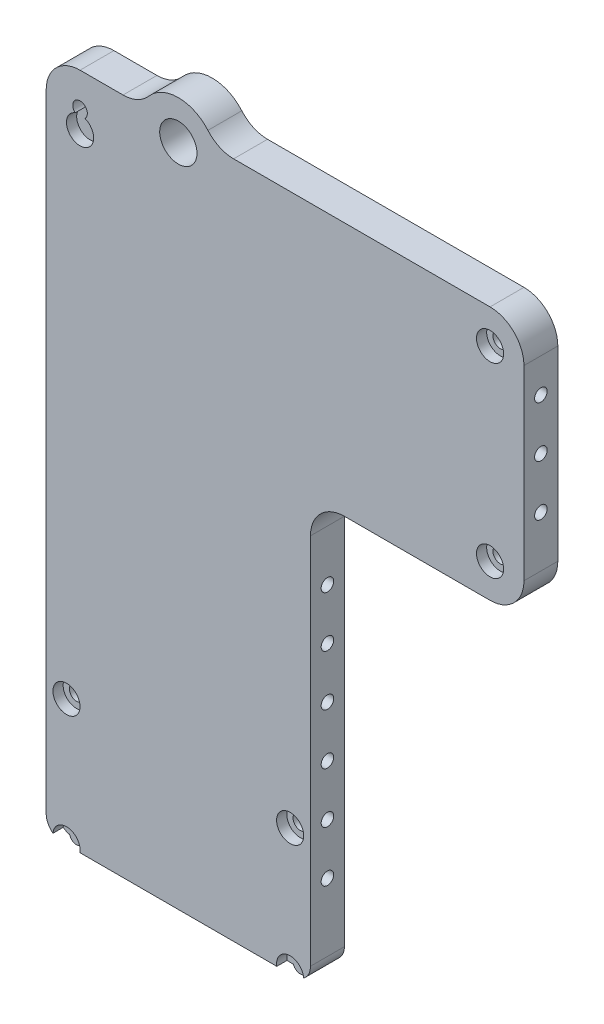
SolidWorks part; units mm, degrees
material "Petg 30% Infill"
ref_plane "Front Plane" through (0, 0, 0) normal (0, 0, 1) x (1, 0, 0)
ref_plane "Top Plane" through (0, 0, 0) normal (0, 1, 0) x (1, 0, 0)
ref_plane "Right Plane" through (0, 0, 0) normal (1, 0, 0) x (0, 0, -1)
sketch "Sketch1" plane through (0, 0, 0) normal (0, 0, 1) x (1, 0, 0)
  line L11 (-3.4368, 18.0423) -> (-3.4368, 128.0423)
  line L12 (6.5632, 138.0423) -> (49.5503, 138.0423)
  line L13 (59.5503, 148.0423) -> (59.5503, 203.0423)
  line L14 (49.5503, 213.0423) -> (-26.1197, 213.0423)
  line L15 (-58.754, 213.0423) -> (-71.4368, 213.0423)
  line L16 (-81.4368, 203.0423) -> (-81.4368, 18.0423)
  line L17 (-76.4368, 13.0423) -> (-8.4368, 13.0423)
  line L18 (-3.4368, 18.0423) -> (-3.4368, 128.0423)
  line L19 (6.5632, 138.0423) -> (49.5503, 138.0423)
  line L20 (59.5503, 148.0423) -> (59.5503, 203.0423)
  line L21 (49.5503, 213.0423) -> (-26.1197, 213.0423)
  line L22 (-58.754, 213.0423) -> (-71.4368, 213.0423)
  line L23 (-81.4368, 203.0423) -> (-81.4368, 18.0423)
  line L24 (-76.4368, 13.0423) -> (-8.4368, 13.0423)
  circle A0 centre (-42.4368, 209.0423) radius 5.5
  arc A1 (-3.4368, 18.0423) -> (-8.4368, 13.0423) centre (-8.4368, 18.0423) cw
  arc A2 (-81.4368, 18.0423) -> (-76.4368, 13.0423) centre (-76.4368, 18.0423) ccw
  circle A3 centre (-42.4368, 209.0423) radius 5.5 construction
  circle A4 centre (-75.4368, 50.376) radius 2.15
  circle A5 centre (-75.4368, 13.7092) radius 2.15
  circle A6 centre (-9.4368, 13.7092) radius 2.15
  arc A7 (6.5632, 138.0423) -> (-3.4368, 128.0423) centre (6.5632, 128.0423) ccw
  arc A8 (49.5503, 138.0423) -> (59.5503, 148.0423) centre (49.5503, 148.0423) ccw
  arc A9 (59.5503, 203.0423) -> (49.5503, 213.0423) centre (49.5503, 203.0423) ccw
  arc A10 (-33.709, 216.5306) -> (-26.1197, 213.0423) centre (-26.1197, 223.0423) ccw
  arc A11 (-33.709, 216.5306) -> (-51.1646, 216.5306) centre (-42.4368, 209.0423) ccw
  arc A12 (-58.754, 213.0423) -> (-51.1646, 216.5306) centre (-58.754, 223.0423) ccw
  arc A13 (-71.4368, 213.0423) -> (-81.4368, 203.0423) centre (-71.4368, 203.0423) ccw
  arc A14 (6.5632, 138.0423) -> (-3.4368, 128.0423) centre (6.5632, 128.0423) ccw
  arc A15 (49.5503, 138.0423) -> (59.5503, 148.0423) centre (49.5503, 148.0423) ccw
  arc A16 (59.5503, 203.0423) -> (49.5503, 213.0423) centre (49.5503, 203.0423) ccw
  arc A17 (-33.709, 216.5306) -> (-26.1197, 213.0423) centre (-26.1197, 223.0423) ccw
  arc A18 (-33.709, 216.5306) -> (-51.1646, 216.5306) centre (-42.4368, 209.0423) ccw
  arc A19 (-58.754, 213.0423) -> (-51.1646, 216.5306) centre (-58.754, 223.0423) ccw
  arc A20 (-71.4368, 213.0423) -> (-81.4368, 203.0423) centre (-71.4368, 203.0423) ccw
  circle A21 centre (-9.4368, 50.376) radius 2.15
  circle A23 centre (-75.4368, 13.7092) radius 2.2 construction
  circle A24 centre (-75.4368, 50.376) radius 2.2 construction
  circle A25 centre (-9.4368, 13.7092) radius 2.2 construction
  circle A26 centre (-9.4368, 50.376) radius 2.2 construction
  arc A35 (-81.4368, 18.0423) -> (-76.4368, 13.0423) centre (-76.4368, 18.0423) ccw
  arc A36 (-81.4368, 18.0423) -> (-76.4368, 13.0423) centre (-76.4368, 18.0423) ccw
  arc A37 (-8.4368, 13.0423) -> (-3.4368, 18.0423) centre (-8.4368, 18.0423) ccw
  arc A38 (-8.4368, 13.0423) -> (-3.4368, 18.0423) centre (-8.4368, 18.0423) ccw
  dimension "D2" = 4.3
  dimension "D3" = 5
  dimension "D1" = 0
extrude "Boss-Extrude1" add sketch "Sketch1" along normal blind 10 contours A1 L18 A14 L19 A15 L20 A16 L21 A17 A18 A19 L22 A20 L23 A2 L24 | A0 | A21 | A6 | A4 | A5
sketch "Sketch2" plane through (0, 0, 10) normal (0, 0, 1) x (1, 0, 0)
  circle A0 centre (-75.4368, 50.376) radius 4
  circle A1 centre (-9.4368, 50.376) radius 4
  circle A2 centre (-9.4368, 13.7092) radius 4
  circle A3 centre (-75.4368, 13.7092) radius 4
  dimension "D1" = 8
extrude "Cut-Extrude1" cut sketch "Sketch2" against normal blind 3
sketch "Sketch3" plane through (0, 0, 0) normal (0, 0, -1) x (-1, 0, 0)
  circle A0 centre (-21.6596, 190.973) radius 1.85
  circle A1 centre (31.0338, 190.3381) radius 1.85
  circle A2 centre (-21.6596, 190.973) radius 4.85
  circle A3 centre (31.0338, 190.3381) radius 4.85
  dimension "D1" = 3.7
  dimension "D2" = 3
extrude "Boss-Extrude2" add sketch "Sketch3" along normal blind 4
sketch "Sketch5" plane through (0, 0, 0) normal (0, 0, -1) x (-1, 0, 0)
  line L0 (47.5919, 184.6852) -> (47.5919, 70.4633) construction
  line L1 (13.3104, 85.2357) -> (47.5919, 85.2357)
  line L2 (13.3104, 85.2357) -> (13.3104, 70.4633)
  line L3 (13.3104, 70.4633) -> (47.5919, 70.4633)
  line L4 (47.5919, 85.2357) -> (47.5919, 70.4633)
  line L5 (47.5919, 70.4633) -> (-38.9159, 70.4633) construction
extrude "Boss-Extrude3" add sketch "Sketch5" along normal blind 4
sketch "Sketch6" plane through (0, 0, 0) normal (0, 0, -1) x (-1, 0, 0)
  line L0 (13.7834, 69.9633) -> (13.7834, 65.6705)
  line L1 (13.7834, 65.6705) -> (52.3848, 65.6705)
  line L2 (52.3848, 65.6705) -> (52.3848, 97.0706)
  line L3 (52.3848, 97.0706) -> (48.0919, 97.0706)
  line L4 (48.0919, 97.0706) -> (48.0919, 69.9633)
  line L5 (48.0919, 69.9633) -> (13.7834, 69.9633)
  line L6 (13.3104, 70.4633) -> (47.5919, 70.4633) construction
  line L7 (47.5919, 70.4633) -> (47.5919, 85.2357) construction
  dimension "D1" = 0.5
  dimension "D2" = 0.5
extrude "Boss-Extrude4" add sketch "Sketch6" along normal blind 6
sketch "Sketch7" plane through (0, 0, -6) normal (0, 0, -1) x (-1, 0, 0)
  line L0 (52.3848, 97.0706) -> (46.0919, 97.0706)
  line L1 (46.0919, 97.0706) -> (46.0919, 71.9633)
  line L2 (46.0919, 71.9633) -> (13.7834, 71.9633)
  line L3 (13.7834, 71.9633) -> (13.7834, 65.6705)
  line L4 (13.7834, 65.6705) -> (52.3848, 65.6705)
  line L5 (52.3848, 65.6705) -> (52.3848, 97.0706)
  line L6 (48.0919, 69.9633) -> (13.7834, 69.9633) construction
  dimension "D1" = 2
extrude "Boss-Extrude5" add sketch "Sketch7" along normal blind 2
chamfer "Chamfer1" distance 2 angle 45 2 edges at (-46.0919, 84.517, -6) (-29.9377, 71.9633, -6)
sketch "Sketch9" plane through (0, 0, 10) normal (0, 0, 1) x (1, 0, 0)
  circle A0 centre (-71.4368, 203.0423) radius 2.15
  circle A1 centre (49.5503, 203.0423) radius 2.15
  arc A2 (59.5503, 203.0423) -> (49.5503, 213.0423) centre (49.5503, 203.0423) ccw construction
  arc A3 (-71.4368, 213.0423) -> (-81.4368, 203.0423) centre (-71.4368, 203.0423) ccw construction
  circle A4 centre (49.5503, 148.0423) radius 2.15
  arc A5 (49.5503, 138.0423) -> (59.5503, 148.0423) centre (49.5503, 148.0423) ccw construction
  dimension "D1" = 4.3
extrude "Cut-Extrude3" cut sketch "Sketch9" against normal blind 20
sketch "Sketch10" plane through (0, 0, 10) normal (0, 0, 1) x (1, 0, 0)
  circle A0 centre (-71.4368, 197.7092) radius 4
  circle A1 centre (49.5503, 203.0423) radius 4
  circle A2 centre (49.5503, 203.0423) radius 2.15 construction
  circle A3 centre (49.5503, 148.0423) radius 4
  arc A4 (49.5503, 138.0423) -> (59.5503, 148.0423) centre (49.5503, 148.0423) ccw construction
  dimension "D1" = 8
extrude "Cut-Extrude4" cut sketch "Sketch10" against normal blind 3
chamfer "Chamfer2" distance 4 angle 45 2 edges at (16.8096, 190.973, 0) (-35.8838, 190.3381, 0)
sketch "Sketch12" plane through (0, 0, 10) normal (0, 0, 1) x (1, 0, 0)
  line L0 (-62.4368, 172.2089) -> (40.5503, 172.2089)
  line L1 (-62.4368, 169.2089) -> (40.5503, 169.2089)
  line L2 (-62.4368, 140.3756) -> (-21.2137, 140.3756)
  line L3 (-62.4368, 143.3756) -> (-15.0522, 143.3756)
  line L4 (-62.4368, 111.5423) -> (-22.4368, 111.5423)
  line L5 (-62.4368, 114.5423) -> (-22.4368, 114.5423)
  line L6 (-62.4368, 82.7089) -> (-22.4368, 82.7089)
  line L7 (-62.4368, 85.7089) -> (-22.4368, 85.7089)
  line L8 (-62.4368, 53.8756) -> (-22.4368, 53.8756)
  line L9 (-62.4368, 56.8756) -> (-22.4368, 56.8756)
  line L10 (-66.4368, 49.8756) -> (-66.4368, 32.0423)
  line L11 (-18.4368, 60.8756) -> (-18.4368, 78.7089)
  line L12 (-18.4368, 89.7089) -> (-18.4368, 107.5423)
  line L13 (-66.4368, 78.7089) -> (-66.4368, 60.8756)
  line L14 (-62.9644, 28.0423) -> (-21.9093, 28.0423)
  line L15 (-18.4368, 30.4424) -> (-18.4368, 128.0423)
  line L16 (6.5632, 153.0423) -> (44.5503, 153.0423)
  line L17 (44.5503, 153.0423) -> (44.5503, 198.0423)
  line L18 (44.5503, 198.0423) -> (-26.1197, 198.0423)
  line L19 (-58.754, 198.0423) -> (-66.4368, 198.0423)
  line L20 (-66.4368, 198.0423) -> (-66.4368, 30.4424)
  line L21 (-62.4368, 28.0423) -> (-22.4368, 28.0423)
  line L22 (-18.4368, 32.0423) -> (-18.4368, 49.8756)
  line L23 (6.5632, 153.0423) -> (40.5503, 153.0423)
  line L24 (44.5503, 157.0423) -> (44.5503, 165.2089)
  line L26 (40.5503, 198.0423) -> (-62.4368, 198.0423)
  line L27 (-66.4368, 194.0423) -> (-66.4368, 176.2089)
  line L28 (-18.4368, 118.5423) -> (-18.4368, 128.0423)
  line L29 (-66.4368, 107.5423) -> (-66.4368, 89.7089)
  line L30 (-66.4368, 136.3756) -> (-66.4368, 118.5423)
  line L31 (-66.4368, 165.2089) -> (-66.4368, 147.3756)
  line L32 (44.5503, 176.2089) -> (44.5503, 194.0423)
  line L33 (-38.7787, 198.0423) -> (-38.7787, 172.2089) construction
  line L34 (-38.7787, 172.2089) -> (-38.7787, 169.2089) construction
  line L35 (-38.7787, 169.2089) -> (-38.7787, 143.3756) construction
  line L36 (-38.7787, 143.3756) -> (-38.7787, 140.3756) construction
  line L37 (-38.7787, 140.3756) -> (-38.7787, 114.5423) construction
  line L38 (-38.7787, 114.5423) -> (-38.7787, 111.5423) construction
  line L39 (-38.7787, 111.5423) -> (-38.7787, 85.7089) construction
  line L40 (-38.7787, 85.7089) -> (-38.7787, 82.7089) construction
  line L41 (-38.7787, 82.7089) -> (-38.7787, 56.8756) construction
  line L42 (-38.7787, 56.8756) -> (-38.7787, 53.8756) construction
  line L43 (-38.7787, 53.8756) -> (-38.7787, 28.0423) construction
  arc A0 (-17.3824, 135.2262) -> (-18.4368, 128.0423) centre (6.5632, 128.0423) ccw
  arc A1 (-62.4368, 53.8756) -> (-66.4368, 49.8756) centre (-62.4368, 49.8756) ccw
  arc A2 (-22.4368, 53.8756) -> (-18.4368, 49.8756) centre (-22.4368, 49.8756) cw
  arc A3 (-22.4368, 56.8756) -> (-18.4368, 60.8756) centre (-22.4368, 60.8756) ccw
  arc A4 (-62.4368, 56.8756) -> (-66.4368, 60.8756) centre (-62.4368, 60.8756) cw
  arc A5 (-62.4368, 82.7089) -> (-66.4368, 78.7089) centre (-62.4368, 78.7089) ccw
  arc A6 (-22.4368, 82.7089) -> (-18.4368, 78.7089) centre (-22.4368, 78.7089) cw
  arc A7 (-62.4368, 28.0423) -> (-66.4368, 32.0423) centre (-62.4368, 32.0423) cw
  arc A8 (-22.4368, 28.0423) -> (-18.4368, 32.0423) centre (-22.4368, 32.0423) ccw
  arc A9 (40.5503, 153.0423) -> (44.5503, 157.0423) centre (40.5503, 157.0423) ccw
  arc A10 (44.5503, 194.0423) -> (40.5503, 198.0423) centre (40.5503, 194.0423) ccw
  arc A12 (-62.4368, 198.0423) -> (-66.4368, 194.0423) centre (-62.4368, 194.0423) ccw
  arc A13 (-22.4368, 85.7089) -> (-18.4368, 89.7089) centre (-22.4368, 89.7089) ccw
  arc A14 (6.5632, 153.0423) -> (-18.4368, 128.0423) centre (6.5632, 128.0423) ccw
  arc A15 (-42.4368, 204.1016) -> (-26.1197, 198.0423) centre (-26.1197, 223.0423) ccw
  arc A16 (-58.754, 198.0423) -> (-42.4368, 204.1016) centre (-58.754, 223.0423) ccw
  arc A17 (6.5632, 153.0423) -> (-12.0707, 144.7089) centre (6.5632, 128.0423) ccw
  arc A18 (-62.4368, 85.7089) -> (-66.4368, 89.7089) centre (-62.4368, 89.7089) cw
  arc A19 (-62.4368, 111.5423) -> (-66.4368, 107.5423) centre (-62.4368, 107.5423) ccw
  arc A20 (-22.4368, 111.5423) -> (-18.4368, 107.5423) centre (-22.4368, 107.5423) cw
  arc A21 (-22.4368, 114.5423) -> (-18.4368, 118.5423) centre (-22.4368, 118.5423) ccw
  arc A22 (-62.4368, 114.5423) -> (-66.4368, 118.5423) centre (-62.4368, 118.5423) cw
  arc A23 (-62.4368, 140.3756) -> (-66.4368, 136.3756) centre (-62.4368, 136.3756) ccw
  arc A24 (-21.2137, 140.3756) -> (-17.3824, 135.2262) centre (-21.2137, 136.3756) cw
  arc A25 (-15.0522, 143.3756) -> (-12.0707, 144.7089) centre (-15.0522, 147.3756) ccw
  arc A26 (-62.4368, 143.3756) -> (-66.4368, 147.3756) centre (-62.4368, 147.3756) cw
  arc A27 (-62.4368, 169.2089) -> (-66.4368, 165.2089) centre (-62.4368, 165.2089) ccw
  arc A28 (40.5503, 169.2089) -> (44.5503, 165.2089) centre (40.5503, 165.2089) cw
  arc A29 (40.5503, 172.2089) -> (44.5503, 176.2089) centre (40.5503, 176.2089) ccw
  arc A30 (-62.4368, 172.2089) -> (-66.4368, 176.2089) centre (-62.4368, 176.2089) cw
  arc A42 (-62.9644, 28.0423) -> (-66.4368, 30.4424) centre (-75.4368, 13.7092) ccw
  arc A43 (-62.9644, 28.0423) -> (-66.4368, 30.4424) centre (-75.4368, 13.7092) ccw
  arc A44 (-18.4368, 30.4424) -> (-21.9093, 28.0423) centre (-9.4368, 13.7092) ccw
  arc A45 (-18.4368, 30.4424) -> (-21.9093, 28.0423) centre (-9.4368, 13.7092) ccw
  point P47 (-66.4368, 53.8756)
  point P55 (-18.4368, 56.8756)
  point P60 (-66.4368, 82.7089)
  point P63 (-18.4368, 82.7089)
  point P66 (-18.4368, 85.7089)
  point P71 (-66.4368, 111.5423)
  point P74 (-18.4368, 111.5423)
  point P77 (-18.4368, 114.5423)
  point P82 (-66.4368, 140.3756)
  point P85 (-15.1828, 140.3756)
  point P92 (-66.4368, 169.2089)
  point P97 (44.5503, 172.2089)
  dimension "D3" = 3
  dimension "D7" = 4
  dimension "D1" = 15
  dimension "D5" = 5
extrude "Cut-Extrude5" cut sketch "Sketch12" against normal blind 6 rebuild error yes
chamfer "Chamfer3" distance 2 angle 45 rebuild error yes
sketch "Sketch13" plane through (-3.4368, 0, 0) normal (1, 0, 0) x (0, 0, -1)
  line L0 (-10, 13.0423) -> (0, 13.0423) construction
  line L1 (-10, 18.0423) -> (0, 18.0423) construction
  circle A0 centre (-5, 38.0423) radius 1.85
  circle A1 centre (-5, 53.0423) radius 1.85
  circle A2 centre (-5, 68.0423) radius 1.85
  circle A3 centre (-5, 83.0423) radius 1.85
  circle A4 centre (-5, 98.0423) radius 1.85
  circle A5 centre (-5, 113.0423) radius 1.85
  point P6 (-5, 18.0423)
  dimension "D2" = 3.7
  dimension "D1" = 25
  dimension "D3" = 6
extrude "Cut-Extrude6" cut sketch "Sketch13" against normal blind 13
sketch "Sketch14" plane through (-81.4368, 0, 0) normal (-1, 0, 0) x (0, 0, 1)
  line L0 (10, 18.0423) -> (0, 18.0423) construction
  line L1 (10, 13.0423) -> (0, 13.0423) construction
  circle A0 centre (5, 38.0423) radius 1.85
  circle A1 centre (5, 53.0423) radius 1.85
  circle A2 centre (5, 68.0423) radius 1.85
  circle A3 centre (5, 83.0423) radius 1.85
  circle A4 centre (5, 98.0423) radius 1.85
  circle A5 centre (5, 113.0423) radius 1.85
  circle A6 centre (5, 128.0423) radius 1.85
  circle A7 centre (5, 143.0423) radius 1.85
  circle A8 centre (5, 158.0423) radius 1.85
  circle A9 centre (5, 173.0423) radius 1.85
  circle A10 centre (5, 188.0423) radius 1.85
  point P5 (5, 18.0423)
  dimension "D1" = 3.7
  dimension "D2" = 25
  dimension "D3" = 11
extrude "Cut-Extrude7" cut sketch "Sketch14" against normal blind 13
sketch "Sketch15" plane through (59.5503, 0, 0) normal (1, 0, 0) x (0, 0, -1)
  line L0 (-10, 203.0423) -> (0, 203.0423) construction
  line L1 (-10, 148.0423) -> (0, 148.0423) construction
  circle A0 centre (-5, 163.0423) radius 1.85
  circle A1 centre (-5, 178.0423) radius 1.85
  circle A2 centre (-5, 193.0423) radius 1.85
  point P4 (-5, 203.0423)
  dimension "D1" = 3.7
  dimension "D2" = 15
  dimension "D3" = 15
  dimension "D4" = 15
extrude "Cut-Extrude8" cut sketch "Sketch15" against normal blind 13
